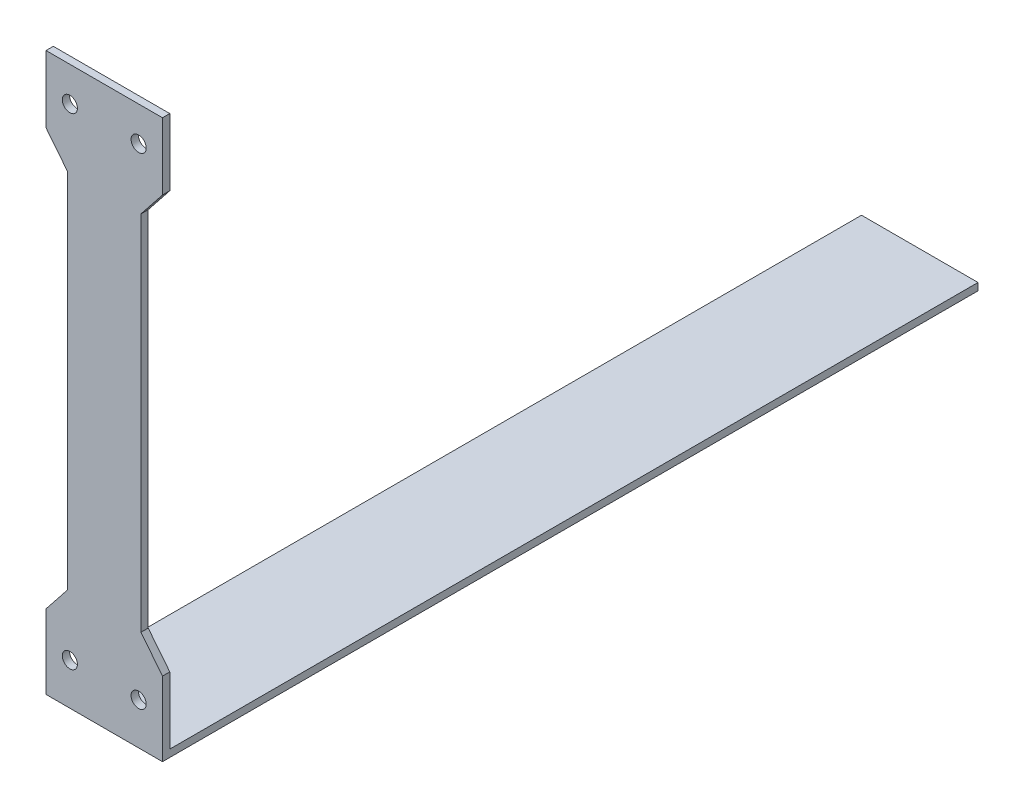
SolidWorks part; units mm, degrees
ref_plane "Front Plane" through (0, 0, 0) normal (0, 0, 1) x (1, 0, 0)
ref_plane "Top Plane" through (0, 0, 0) normal (0, 1, 0) x (1, 0, 0)
ref_plane "Right Plane" through (0, 0, 0) normal (1, 0, 0) x (0, 0, -1)
sketch "Sketch1" plane through (0, 0, 0) normal (0, 0, 1) x (1, 0, 0)
  line L0 (-117, 99.5) -> (-103.5, 116.5) construction
  line L1 (-146.5, 116.5) -> (-133, 99.5) construction
  line L2 (-133, 99.5) -> (-117, 99.5) construction
  line L3 (-117, 99.5) -> (-103.5, 116.5)
  line L4 (-146.5, 116.5) -> (-133, 99.5)
  line L5 (-133, 99.5) -> (-117, 99.5) construction
  line L6 (-250, 120) -> (0, 120) construction
  line L7 (-146.5, 120) -> (-103.5, 120)
  line L8 (0, 0) -> (-250, 0) construction
  line L9 (-103.5, 3.5) -> (-117, 20.5) construction
  line L10 (-117, 20.5) -> (-133, 20.5) construction
  line L11 (-133, 20.5) -> (-146.5, 3.5) construction
  line L12 (-103.5, 0) -> (-146.5, 0)
  line L13 (-103.5, 3.5) -> (-117, 20.5)
  line L14 (-117, 20.5) -> (-133, 20.5) construction
  line L15 (-133, 20.5) -> (-146.5, 3.5)
  line L16 (-103.5, 3.5) -> (-103.5, 0)
  line L17 (-137.7, 14.5815) -> (-137.7, 0)
  line L18 (-146.5, 3.5) -> (-146.5, 0)
  line L19 (-103.5, 116.5) -> (-103.5, 120)
  line L20 (-146.5, 116.5) -> (-146.5, 120)
  line L21 (-117, 20.5) -> (-117, 99.5)
  line L22 (-133, 99.5) -> (-133, 20.5)
  line L23 (-125, 0) -> (-125, 120) construction
  line L24 (-112.3, 14.5815) -> (-112.3, 0)
  line L25 (-137.7, 105.4185) -> (-137.7, 120)
  line L26 (-112.3, 120) -> (-112.3, 105.4185)
  arc A0 (-134.15, 112.5) -> (-130.85, 112.5) centre (-132.5, 112.5) ccw construction
  arc A1 (-130.85, 112.5) -> (-134.15, 112.5) centre (-132.5, 112.5) ccw construction
  arc A2 (-119.15, 112.5) -> (-115.85, 112.5) centre (-117.5, 112.5) ccw construction
  arc A3 (-115.85, 112.5) -> (-119.15, 112.5) centre (-117.5, 112.5) ccw construction
  arc A4 (-134.15, 112.5) -> (-130.85, 112.5) centre (-132.5, 112.5) ccw
  arc A5 (-130.85, 112.5) -> (-134.15, 112.5) centre (-132.5, 112.5) ccw
  arc A6 (-119.15, 112.5) -> (-115.85, 112.5) centre (-117.5, 112.5) ccw
  arc A7 (-115.85, 112.5) -> (-119.15, 112.5) centre (-117.5, 112.5) ccw
  arc A8 (-115.85, 7.5) -> (-119.15, 7.5) centre (-117.5, 7.5) ccw construction
  arc A9 (-119.15, 7.5) -> (-115.85, 7.5) centre (-117.5, 7.5) ccw construction
  arc A10 (-134.15, 7.5) -> (-130.85, 7.5) centre (-132.5, 7.5) ccw construction
  arc A11 (-130.85, 7.5) -> (-134.15, 7.5) centre (-132.5, 7.5) ccw construction
  arc A12 (-115.85, 7.5) -> (-119.15, 7.5) centre (-117.5, 7.5) ccw
  arc A13 (-119.15, 7.5) -> (-115.85, 7.5) centre (-117.5, 7.5) ccw
  arc A14 (-134.15, 7.5) -> (-130.85, 7.5) centre (-132.5, 7.5) ccw
  arc A15 (-130.85, 7.5) -> (-134.15, 7.5) centre (-132.5, 7.5) ccw
  dimension "D1" = 12.7
extrude "Boss-Extrude1" add sketch "Sketch1" along normal blind 1.5875 contours L24 L13 L21 L3 L19 L7 L20 L4 L22 L15 L17 L12 A15 A14 A13 A12 A7 A6 A5 A4 region at (-125, 60, 0)
sketch "Sketch2" plane through (0, 0, 0) normal (0, 1, 0) x (1, 0, 0)
  line L0 (-112.3, -1.5875) -> (-112.3, 176.2125)
  line L1 (-112.3, 176.2125) -> (-137.7, 176.2125)
  line L2 (-137.7, 176.2125) -> (-137.7, -1.5875)
  line L3 (-137.7, -1.5875) -> (-112.3, -1.5875) construction
  line L5 (-137.7, -1.5875) -> (-112.3, -1.5875)
  dimension "D1" = 177.8
extrude "Boss-Extrude2" add sketch "Sketch2" against normal blind 1.5875
